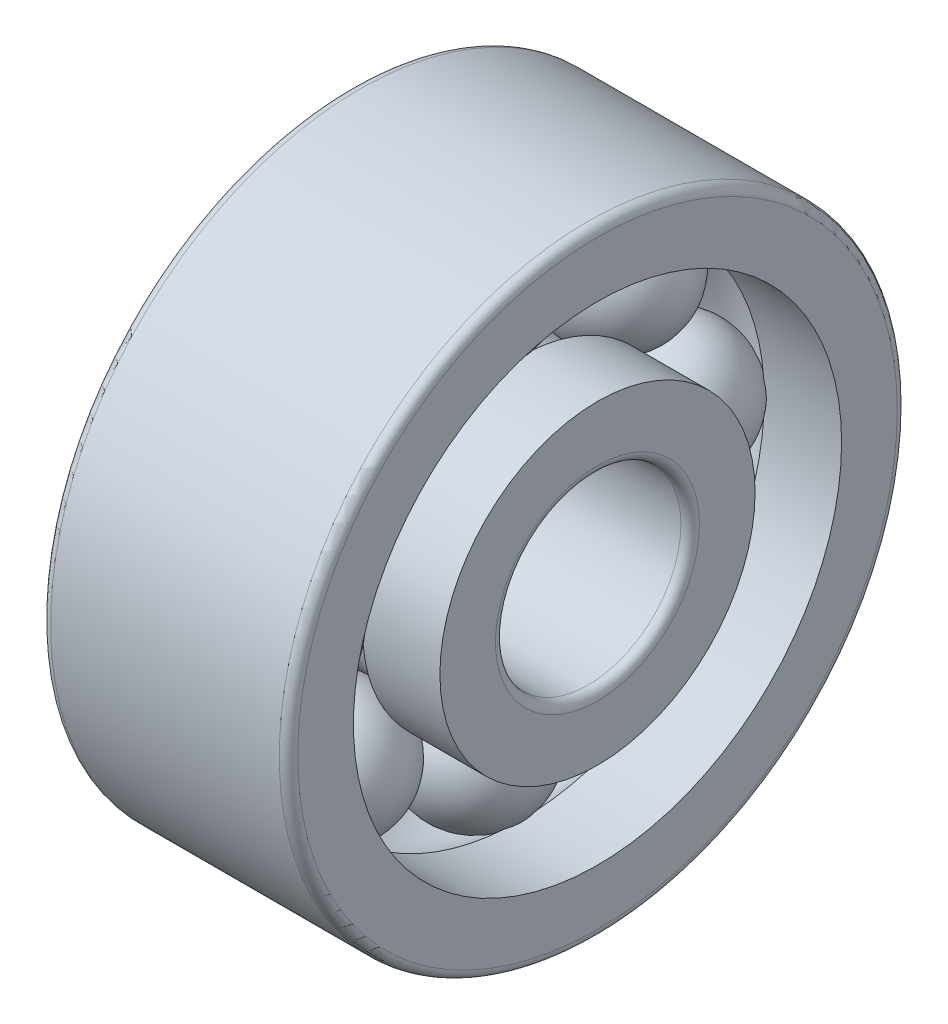
SolidWorks part; units mm, degrees
ref_plane "Plane1" through (0, 0, 0) normal (0, 0, 1) x (1, 0, 0)
ref_plane "Plane2" through (0, 0, 0) normal (0, 1, 0) x (1, 0, 0)
ref_plane "Plane3" through (0, 0, 0) normal (1, 0, 0) x (0, 0, -1)
sketch "Clipboard" plane through (0, 0, 0) normal (0, 0, 1) x (1, 0, 0)
  line L0 (-10, 0) -> (10, 0) construction
  line L1 (0, 0) -> (22.1431, -3.112)
  line L2 (0, 0) -> (3.2184, 0.4523)
  line L3 (0, 0) -> (22.1431, -3.112)
  line L4 (0, 0) -> (-22.3573, -0.3902)
  dimension "BallCLRad" = 3.25
sketch "CagSpiSke" plane through (0, 0, 0) normal (0, 0, 1) x (1, 0, 0)
  line L0 (0.105, 3.075) -> (0.105, 3.425)
  line L1 (0.105, 3.425) -> (-0.105, 3.425)
  line L2 (-0.105, 3.425) -> (-0.105, 3.075)
  line L3 (-0.105, 3.075) -> (0.105, 3.075)
  line L4 (-20.6375, 0) -> (20.6375, 0) construction
  line L5 (0, 0) -> (0, 23.7692) construction
  dimension "OD" = 6.85
  dimension "ID" = 6.15
revolve "CageSpine" add sketch "CagSpiSke" angle 0.001 about L4 reverse direction yes
ref_axis "Axis1" through (-50, 0, 0) along (1, 0, 0)
sketch "CagBalSke" plane through (0, 0, 0) normal (0, 0, 1) x (1, 0, 0)
  line L0 (-1.155, 3.25) -> (1.155, 3.25)
  line L1 (-1.905, 3.25) -> (1.905, 3.25) construction
  line L2 (-10, 0) -> (10, 0) construction
  line L3 (0, 0) -> (0, 24) construction
  arc A0 (1.155, 3.25) -> (-1.155, 3.25) centre (0, 3.25) cw
  dimension "BallCLRad" = 3.25
revolve "CageBall" [suppressed] add sketch "CagBalSke" angle 360 about L1 reverse direction yes
pattern_circular "CageBalls" [suppressed] count 8 every 45 about axis through (-50, 0, 0) along (1, 0, 0)
sketch "CagTrmODSke" plane through (0, 0, 0) normal (0, 0, 1) x (1, 0, 0)
  line L0 (1.156, 3.425) -> (1.156, 4.406)
  line L1 (1.156, 4.406) -> (-1.156, 4.406)
  line L2 (-1.156, 4.406) -> (-1.156, 3.425)
  line L3 (-1.156, 3.425) -> (1.156, 3.425)
  line L4 (-20.6375, 0) -> (20.6375, 0) construction
  line L5 (0, 0) -> (0, 25) construction
  dimension "Width" = 2.312
  dimension "ID" = 6.85
  dimension "OD" = 8.812
revolve "CageTrimOD" [suppressed] cut sketch "CagTrmODSke" angle 360 about L4 reverse direction yes
sketch "CagTrmIDSke" plane through (0, 0, 0) normal (0, 0, 1) x (1, 0, 0)
  line L0 (1.156, 2.096) -> (1.156, 3.075)
  line L1 (1.156, 3.075) -> (-1.156, 3.075)
  line L2 (-1.156, 3.075) -> (-1.156, 2.096)
  line L3 (-1.156, 2.096) -> (1.156, 2.096)
  line L4 (-20.6375, 0) -> (20.6375, 0) construction
  line L5 (0, 0) -> (0, 25) construction
  dimension "Width" = 2.312
  dimension "ID" = 4.192
  dimension "OD" = 6.15
revolve "CageTrimID" [suppressed] cut sketch "CagTrmIDSke" angle 360 about L4 reverse direction yes
sketch "BalSimSke" plane through (0, 0, 0) normal (0, 0, 1) x (1, 0, 0)
  line L0 (-10, 0) -> (10, 0) construction
  line L1 (-10, 3.25) -> (10, 3.25) construction
  line L2 (0, 0) -> (0, 23) construction
  circle A0 centre (0, 3.25) radius 1.05
  dimension "BallCLRad" = 3.25
  dimension "Ball_diameter" = 2.1
revolve "BallsSimplified" [suppressed] add sketch "BalSimSke" angle 360 about L0
sketch "BalDetSke" plane through (0, 0, 0) normal (0, 0, 1) x (1, 0, 0)
  line L0 (-1.05, 3.25) -> (1.05, 3.25)
  line L1 (-1.905, 3.25) -> (1.905, 3.25) construction
  line L2 (0, 0) -> (0, 25) construction
  arc A0 (1.05, 3.25) -> (-1.05, 3.25) centre (0, 3.25) cw
  dimension "BallCLRad" = 3.25
  dimension "Ball_diameter" = 2.1
revolve "BallDetailed" add sketch "BalDetSke" angle 360 about L1 reverse direction yes
sketch "InnRacSke" plane through (0, 0, 0) normal (0, 0, 1) x (1, 0, 0)
  line L0 (-0.7487, 2.55) -> (-2, 2.55)
  line L1 (-2, 2.55) -> (-2, 1.65)
  line L2 (-1.85, 1.5) -> (1.85, 1.5)
  line L3 (2, 1.65) -> (2, 2.55)
  line L4 (2, 2.55) -> (0.7487, 2.55)
  line L5 (-20.6375, 0) -> (20.6375, 0) construction
  line L6 (0, 0) -> (0, 30) construction
  arc A0 (-2, 1.65) -> (-1.85, 1.5) centre (-1.85, 1.65) ccw
  arc A1 (1.85, 1.5) -> (2, 1.65) centre (1.85, 1.65) ccw
  arc A2 (0.7487, 2.55) -> (-0.7487, 2.55) centre (0, 3.25) cw
  dimension "BallCLRad" = 3.25
  dimension "Fillet_radius" = 0.15
  dimension "Ball_diameter" = 2.05
  dimension "ID" = 3
  dimension "OD" = 5.1
  dimension "Width" = 4
revolve "InnerRace" add sketch "InnRacSke" angle 360 about L5 reverse direction yes
sketch "OutRacSke" plane through (0, 0, 0) normal (0, 0, 1) x (1, 0, 0)
  line L0 (-0.7487, 3.95) -> (-2, 3.95)
  line L1 (-2, 3.95) -> (-2, 4.85)
  line L2 (-1.85, 5) -> (1.85, 5)
  line L3 (2, 4.85) -> (2, 3.95)
  line L4 (2, 3.95) -> (0.7487, 3.95)
  line L5 (-20.6375, 0) -> (20.6375, 0) construction
  line L6 (0, 0) -> (0, 30) construction
  arc A0 (-2, 4.85) -> (-1.85, 5) centre (-1.85, 4.85) cw
  arc A1 (1.85, 5) -> (2, 4.85) centre (1.85, 4.85) cw
  arc A2 (0.7487, 3.95) -> (-0.7487, 3.95) centre (0, 3.25) ccw
  dimension "BallCLRad" = 3.25
  dimension "Fillet_radius" = 0.15
  dimension "Ball_diameter" = 2.05
  dimension "Width" = 4
revolve "OuterRace" add sketch "OutRacSke" angle 360 about L5 reverse direction yes
pattern_circular "BallsDetailed" count 8 every 45 about axis through (-50, 0, 0) along (1, 0, 0) of "BallDetailed"
equation "\"BallCLRad@Clipboard\" = ( \"OD@OutRacSke\" + \"ID@InnRacSke\" ) / 4"
equation "\"BallCLRad@BalSimSke\" = \"BallCLRad@Clipboard\""
equation "\"BallCLRad@BalDetSke\" = \"BallCLRad@Clipboard\""
equation "\"BallCLRad@InnRacSke\" = \"BallCLRad@Clipboard\""
equation "\"BallCLRad@OutRacSke\" = \"BallCLRad@Clipboard\""
equation "\"Ball_diameter@InnRacSke\" = \"Ball_diameter@BalDetSke\" - 0.05"
equation "\"Ball_diameter@OutRacSke\" = \"Ball_diameter@BalDetSke\" - 0.05"
equation "\"Ball_diameter@BalSimSke\" = \"Ball_diameter@BalDetSke\""
equation "\"Width@OutRacSke\" = \"Width@InnRacSke\""
equation "\"Fillet_radius@OutRacSke\" = \"Fillet_radius@InnRacSke\""
equation "\"Max_count@Clipboard\" = int( 3.14159265 / atn(( \"Ball_diameter@BalDetSke\" / 2) / sqr( \"BallCLRad@Clipboard\"  *  \"BallCLRad@Clipboard\" - ( \"Ball_diameter@BalDetSke\" / 2) *  ( \"Ball_diameter@BalDetSke\" / 2))))"
equation "\"Max_count@Clipboard\" = ((sgn( \"Max_count@Clipboard\" - \"Count@Clipboard\" )-1)*( \"Max_count@Clipboard\" - \"Count@Clipboard\" ))/-2+ \"Count@Clipboard\""
equation "\"Count@BallsDetailed\" = int( \"Show_count@Clipboard\" ) "
equation "\"Count@BallsDetailed\" = ((sgn( \"Count@BallsDetailed\" - \"Max_count@Clipboard\" )-1)*( \"Count@BallsDetailed\" - \"Max_count@Clipboard\" ))/-2+ \"Max_count@Clipboard\""
equation "\"Count@BallsDetailed\" = ((sgn( \"Count@BallsDetailed\" - \"Min_count@Clipboard\" )+1)*( \"Count@BallsDetailed\" - \"Min_count@Clipboard\"))/2 +\"Min_count@Clipboard\""
equation "\"Angle@BallsDetailed\" = 360.0 / \"Max_count@Clipboard\""
equation "\"BallCLRad@CagBalSke\" = \"BallCLRad@Clipboard\""
equation "\"Count@CageBalls\" = \"Count@BallsDetailed\""
equation "\"Angle@CageBalls\" = \"Angle@BallsDetailed\""
equation "\"Angle@CageSpine\" =  \"Angle@CageBalls\" * ( \"Count@CageBalls\" -1 + int( \"Count@CageBalls\" / \"Max_count@Clipboard\" ) )  + 0.001 -  int( \"Count@CageBalls\" / \"Max_count@Clipboard\" ) * 0.001"
equation "\"Angle@CageSpine\" =  \"Angle@CageSpine\" * int( \"Min_count@Clipboard\" / 2) + int(1 / \"Min_count@Clipboard\")  * 0.001"
equation "\"CageWallOD@CagBalSke\" =  \"Ball_diameter@BalDetSke\" * 1.1"
equation "\"Thickness@CagSpiSke\" =  \"Ball_diameter@BalDetSke\" * 0.1"
equation "\"OD@CagTrmODSke\" = \"BallCLRad@Clipboard\" * 2 + \"CageWallOD@CagBalSke\" + 0.002"
equation "\"ID@CagTrmODSke\" = \"BallCLRad@Clipboard\" * 2 + \"Ball_diameter@BalDetSke\" / 6"
equation "\"OD@CagTrmIDSke\" = \"BallCLRad@Clipboard\" * 2 - \"Ball_diameter@BalDetSke\" / 6"
equation "\"ID@CagTrmIDSke\" = \"BallCLRad@Clipboard\" * 2 - \"CageWallOD@CagBalSke\" + 0.002"
equation "\"OD@CagSpiSke\" = \"ID@CagTrmODSke\""
equation "\"ID@CagSpiSke\" = \"OD@CagTrmIDSke\""
equation "\"Width@CagTrmODSke\" = \"CageWallOD@CagBalSke\" + 0.002"
equation "\"Width@CagTrmIDSke\" = \"CageWallOD@CagBalSke\" + 0.002"
